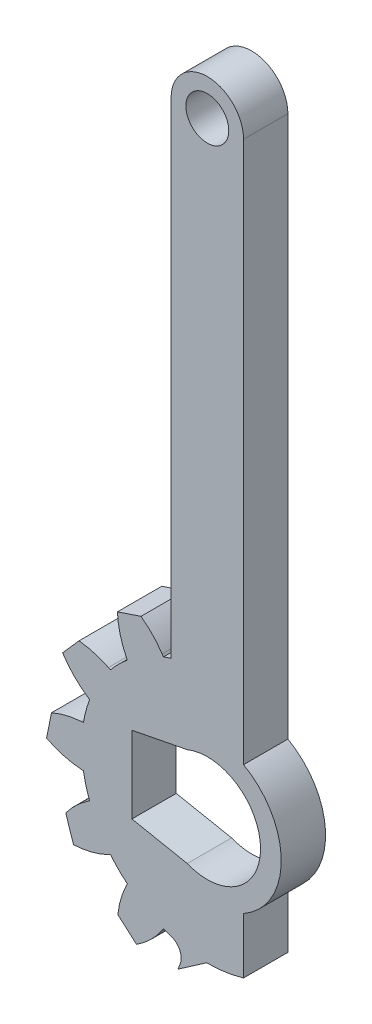
SolidWorks part; units mm, degrees
ref_plane "Front Plane" through (0, 0, 0) normal (0, 0, 1) x (1, 0, 0)
ref_plane "Top Plane" through (0, 0, 0) normal (0, 1, 0) x (1, 0, 0)
ref_plane "Right Plane" through (0, 0, 0) normal (1, 0, 0) x (0, 0, -1)
ref_plane "Plane1" through (0, 0, 1.9) normal (0, 0, 1) x (1, 0, 0)
sketch "Sketch1" plane through (0, 0, 1.9) normal (0, 0, 1) x (1, 0, 0)
  line L0 (2.45, -8.1393) -> (2.45, -4.3586)
  line L1 (2.45, 4.3586) -> (2.45, 41)
  line L2 (-2.45, 41) -> (-2.45, 8.1393)
  line L3 (-2.9677, 7.9651) -> (-3.0542, 8.0933)
  line L4 (-5.4819, 6.6916) -> (-5.4141, 6.5527)
  line L5 (-6.5527, 5.4141) -> (-6.6916, 5.4819)
  line L6 (-8.0933, 3.0542) -> (-7.9651, 2.9677)
  line L7 (-8.3818, 1.4124) -> (-8.5361, 1.4016)
  line L8 (-8.5361, -1.4016) -> (-8.3818, -1.4124)
  line L9 (-7.9651, -2.9677) -> (-8.0933, -3.0542)
  line L10 (-6.6916, -5.4819) -> (-6.5527, -5.4141)
  line L11 (-5.4141, -6.5527) -> (-5.4819, -6.6916)
  line L12 (-3.0542, -8.0933) -> (-2.9677, -7.9651)
  line L13 (-1.4371, -8.3776) -> (-1.9842, -9.839)
  line L17 (-1.9842, -9.839) -> (-0.053, -8.4998)
  arc A0 (2.45, -4.3586) -> (2.45, 4.3586) centre (0, 0) ccw
  arc A1 (2.45, 41) -> (-2.45, 41) centre (0, 41) ccw
  arc A2 (-2.45, 8.1393) -> (-2.9677, 7.9651) centre (0, 0) ccw
  arc A3 (-3.0542, 8.0933) -> (-5.9946, 10.3829) centre (-8.0284, 4.7381) ccw
  arc A4 (-5.9946, 10.3829) -> (-5.4819, 6.6916) centre (-0.0891, 9.3218) ccw
  arc A5 (-5.4141, 6.5527) -> (-6.5527, 5.4141) centre (0, 0) ccw
  arc A6 (-6.6916, 5.4819) -> (-10.3829, 5.9946) centre (-9.3218, 0.0891) ccw
  arc A7 (-10.3829, 5.9946) -> (-8.0933, 3.0542) centre (-4.7381, 8.0284) ccw
  arc A8 (-7.9651, 2.9677) -> (-8.3818, 1.4124) centre (0, 0) ccw
  arc A9 (-8.5361, 1.4016) -> (-11.9891, 0) centre (-8.1175, -4.5837) ccw
  arc A10 (-11.9891, 0) -> (-8.5361, -1.4016) centre (-8.1175, 4.5837) ccw
  arc A11 (-8.3818, -1.4124) -> (-7.9651, -2.9677) centre (0, 0) ccw
  arc A12 (-8.0933, -3.0542) -> (-10.3829, -5.9946) centre (-4.7381, -8.0284) ccw
  arc A13 (-10.3829, -5.9946) -> (-6.6916, -5.4819) centre (-9.3218, -0.0891) ccw
  arc A14 (-6.5527, -5.4141) -> (-5.4141, -6.5527) centre (0, 0) ccw
  arc A15 (-5.4819, -6.6916) -> (-5.9946, -10.3829) centre (-0.0891, -9.3218) ccw
  arc A16 (-5.9946, -10.3829) -> (-3.0542, -8.0933) centre (-8.0284, -4.7381) ccw
  arc A17 (-2.9677, -7.9651) -> (-1.4371, -8.3776) centre (0, 0) ccw
  circle A18 centre (0, 41) radius 1.45
  arc A19 (-2.45, 8.1393) -> (-1.4371, -8.3776) centre (0, 0) cw construction
  arc A22 (-0.053, -8.4998) -> (2.45, -8.1393) centre (0, 0) ccw
  dimension "D1" = 5
  dimension "D2" = 0.0891
  dimension "D3" = 8.5
  dimension "D4" = 6
  dimension "D13" = 2.9
  dimension "D14" = 34.736
  dimension "D17" = 0.053
  dimension "D18" = 1.4371
  dimension "D19" = 1.9842
  dimension "D5" = 2.9677
  dimension "D6" = 3.0542
  dimension "D7" = 4.7381
  dimension "D8" = 5.4141
  dimension "D9" = 5.4819
  dimension "D10" = 6.5527
  dimension "D11" = 8.1175
  dimension "D12" = 8.3818
  dimension "D15" = 41
  dimension "4,9" = 4.9
extrude "Boss-Extrude1" add sketch "Sketch1" against normal blind 3
ref_plane "Plane2" through (0, 0, 1.9) normal (0, 0, -1) x (-1, 0, 0)
sketch "Sketch4" plane through (0, 0, 1.9) normal (0, 0, 1) x (1, 0, 0)
  line L0 (-5.1029, -2.6) -> (-1.3588, -3.3337)
  line L1 (-1.3588, 3.3337) -> (-5.1029, 2.6)
  line L2 (-5.1029, 2.6) -> (-5.1029, -2.6)
  arc A0 (-1.3588, -3.3337) -> (-1.3588, 3.3337) centre (0, 0) cw
extrude "Cut-Extrude2" cut sketch "Sketch4" against normal through all
sketch "Sketch5" plane through (0, 0, 0) normal (0, 1, 0) x (1, 0, 0)
  line L0 (3.6, 1.1) -> (0, 1.1)
  line L1 (0, 1.1) -> (0, -1.9)
  line L2 (0, -1.9) -> (3.6, -1.9)
  line L3 (3.6, -1.9) -> (3.6, 1.1)
  line L4 (0, 1.1) -> (0, -1.9) construction
  line L5 (2.45, 1.1) -> (-2.45, 1.1) construction
revolve "Cut-Revolve1" cut sketch "Sketch5" angle 360 about L4 reverse direction yes
chamfer "Chamfer1" distance 1.4124 angle 61.288 5 edges at (-10.3829, -5.9946, 0.4) (-5.9946, -10.3829, 0.4) (-11.9891, 0, 0.4) (-10.3829, 5.9946, 0.4) (-5.9946, 10.3829, 0.4) first distance on face at (-8.5169, -5.8852, 0.4) first distance on face at (-4.4332, -9.3551, 0.4) first distance on face at (-10.3184, -0.8383, 0.4) first distance on face at (-9.3551, 4.4332, 0.4) first distance on face at (-5.8852, 8.5169, 0.4)
fillet "Fillet1" radius 1 1 edges at (-1.4371, -8.3776, 0.4) tangent propagation no
